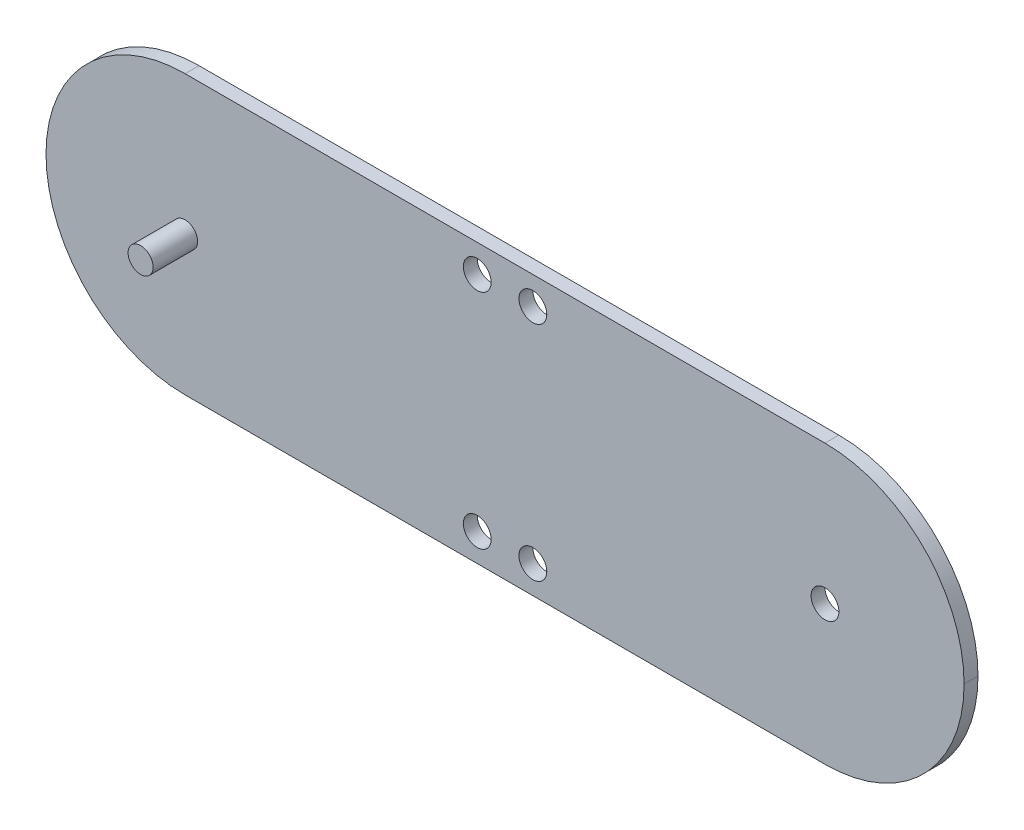
SolidWorks part; units mm, degrees
ref_plane "Front Plane" through (0, 0, 0) normal (0, 0, 1) x (1, 0, 0)
ref_plane "Top Plane" through (0, 0, 0) normal (0, 1, 0) x (1, 0, 0)
ref_plane "Right Plane" through (0, 0, 0) normal (1, 0, 0) x (0, 0, -1)
sketch "Sketch1" plane through (0, 0, 0) normal (0, 0, 1) x (1, 0, 0)
  line L1 (82.5, 25) -> (-82.5, 25)
  line L2 (82.5, 25) -> (82.5, -25)
  line L3 (82.5, -25) -> (-82.5, -25)
  line L4 (-82.5, 25) -> (-82.5, -25)
  line L5 (82.5, 25) -> (-82.5, -25) construction
  line L6 (82.5, -25) -> (-82.5, 25) construction
  point P0 (0, 0)
  dimension "D1" = 50
  dimension "D2" = 165
extrude "Boss-Extrude1" add sketch "Sketch1" along normal blind 2.5
fillet "Fillet1" radius 25 4 edges at (-82.5, -25, 1.25) (-82.5, 25, 1.25) (82.5, -25, 1.25) (82.5, 25, 1.25)
sketch "Sketch2" plane through (0, 0, 2.5) normal (0, 0, 1) x (1, 0, 0)
  line L0 (0, 0) -> (0, 20)
  line L1 (0, 20) -> (-5, 20)
  line L2 (-5, 20) -> (5, 20)
  circle A0 centre (-5, 20) radius 2.5
  circle A1 centre (5, 20) radius 2.5
  dimension "D4" = 5
  dimension "D5" = 5
  dimension "D1" = 20
  dimension "D2" = 5
  dimension "D3" = 10
extrude "Cut-Extrude1" cut sketch "Sketch2" against normal blind 2.5 contours A0 | A1 region at (-7.4293, 20, 2.5) region at (5, 22.4293, 2.5)
mirror "Mirror1" about plane through (0, 0, 0) normal (0, 1, 0) of "Cut-Extrude1"
sketch "Sketch3" plane through (0, 0, 0) normal (0, 0, -1) x (-1, 0, 0)
  line L0 (0, 0) -> (-57.5, 0)
  circle A0 centre (-57.5, 0) radius 2.5
  dimension "D2" = 5
  dimension "D1" = 57.5
extrude "Cut-Extrude2" cut sketch "Sketch3" against normal blind 2.5 contours A0 region at (59.9293, 0, 0)
sketch "Sketch4" plane through (0, 0, 2.5) normal (0, 0, 1) x (1, 0, 0)
  line L0 (0, 0) -> (-57.5, 0)
  circle A0 centre (-57.5, 0) radius 2.25
  dimension "D2" = 4.5
  dimension "D1" = 57.5
extrude "Boss-Extrude2" add sketch "Sketch4" along normal blind 8 contours A0 region at (-59.6864, 0, 2.5)
